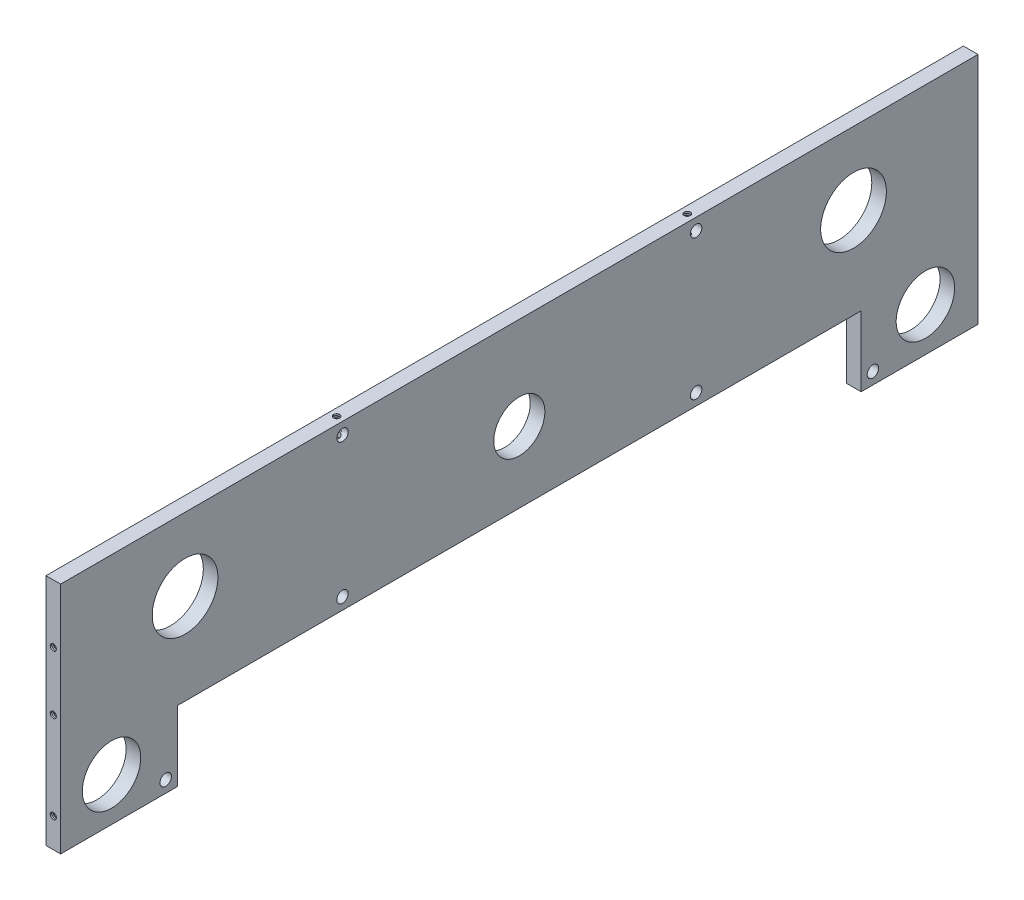
SolidWorks part; units mm, degrees
material "6061-T6 (SS)"
ref_plane "Front Plane" through (0, 0, 0) normal (0, 0, 1) x (1, 0, 0)
ref_plane "Top Plane" through (0, 0, 0) normal (0, 1, 0) x (1, 0, 0)
ref_plane "Right Plane" through (0, 0, 0) normal (1, 0, 0) x (0, 0, -1)
sketch "Sketch1" plane through (0, 0, 0) normal (1, 0, 0) x (0, 0, -1)
  line L1 (-199.39, 50.8) -> (199.39, 50.8)
  line L2 (-199.39, 50.8) -> (-199.39, -50.8)
  line L3 (-199.39, -50.8) -> (199.39, -50.8)
  line L4 (199.39, 50.8) -> (199.39, -50.8)
  line L5 (-199.39, 50.8) -> (199.39, -50.8) construction
  line L6 (-199.39, -50.8) -> (199.39, 50.8) construction
  point P0 (0, 0)
  dimension "D1" = 101.6
  dimension "D2" = 398.78
extrude "Boss-Extrude1" add sketch "Sketch1" along normal blind 6.35
sketch "Sketch2" plane through (6.35, 0, 0) normal (1, 0, 0) x (0, 0, -1)
  line L0 (-199.39, -50.8) -> (199.39, -50.8) construction
  line L1 (-145.2858, 19.1748) -> (0, 10.4973) construction
  line L2 (199.39, 50.8) -> (-199.39, 50.8) construction
  line L3 (0, 10.4973) -> (145.2858, 19.1748) construction
  line L4 (2.4449, 27.4682) -> (-141.1117, 48.1494) construction
  line L5 (0.4075, -6.6439) -> (-144.5902, -10.0906) construction
  line L10 (1.5901, 21.5351) -> (-141.9664, 42.2162) construction
  line L11 (-199.39, 50.8) -> (-199.39, -50.8) construction
  line L12 (-148.59, -50.8) -> (0, -50.8)
  line L13 (-148.59, -50.8) -> (-148.59, -20.32)
  line L14 (-148.59, -20.32) -> (148.59, -20.32)
  line L15 (0, -50.8) -> (0, -20.32) construction
  line L16 (199.39, -50.8) -> (199.39, 50.8) construction
  line L17 (-162.4251, -40.5407) -> (-132.2012, 11.5885) construction
  line L18 (0.265, -0.6512) -> (-144.7326, -4.0979) construction
  line L19 (-177.2583, -31.9405) -> (-199.39, -31.9405) construction
  line L20 (-177.2583, -31.9405) -> (-158.1418, -43.0925) construction
  line L21 (148.59, -50.8) -> (148.59, -20.32)
  line L22 (0, -50.8) -> (148.59, -50.8)
  line L23 (-77.0202, -8.4844) -> (-76.9825, -10.0714) construction
  line L24 (-77.5914, 40.6024) -> (-77.8178, 39.0311) construction
  circle A1 centre (-145.2858, 19.1748) radius 14.2875
  circle A2 centre (145.2858, 19.1748) radius 14.2875
  circle A3 centre (-145.2858, 19.1748) radius 29.2737 construction
  circle A4 centre (0, 10.4973) radius 30.48 construction
  circle A5 centre (145.2858, 19.1748) radius 29.2737 construction
  circle A11 centre (-177.2583, -31.9405) radius 12.7
  circle A12 centre (176.53, -31.9405) radius 12.7
  circle A13 centre (0, 10.4973) radius 11.1125
  circle A14 centre (-177.2583, -31.9405) radius 20.6375 construction
  circle A15 centre (-177.2583, -31.9405) radius 17.1461 construction
  circle A16 centre (-145.2858, 19.1748) radius 15.1248 construction
  circle A17 centre (0, 10.4973) radius 17.1461 construction
  circle A18 centre (34.3662, 10.4973) radius 8.7754 construction
  circle A19 centre (-153.715, -45.675) radius 5.125 construction
  circle A20 centre (-153.715, -45.675) radius 2.4892
  circle A21 centre (-76.8607, 45.675) radius 5.125 construction
  circle A22 centre (-76.8607, -15.195) radius 5.125 construction
  circle A23 centre (-76.8607, -15.195) radius 2.4892
  circle A24 centre (-76.8607, 45.675) radius 2.4892
  circle A25 centre (76.8607, 45.675) radius 2.4892
  circle A26 centre (76.8607, -15.195) radius 2.4892
  circle A27 centre (153.715, -45.675) radius 2.4892
  circle A28 centre (34.3662, 10.4973) radius 22.15 construction
  point P11 (0, 0)
  point P12 (0, -19.9827)
  point P14 (0, 40.9773)
  point P52 (-197.8958, -31.9405)
  point P56 (-159.5733, 19.1748)
  dimension "D1" = 28.575
  dimension "D5" = 58.5474
  dimension "D7" = 9.8227
  dimension "D14" = 25.4
  dimension "D15" = 60.2911
  dimension "D17" = 25.4
  dimension "D20" = 22.225
  dimension "D21" = 28.575
  dimension "D22" = 60.96
  dimension "D23" = 41.275
  dimension "D27" = 34.2921
  dimension "D28" = 30.2496
  dimension "D12" = 17.5508
  dimension "D13" = 10.25
  dimension "D29" = 4.9784
  dimension "D26" = 1.5875
  dimension "D30" = 4.9784
  dimension "D31" = 44.3
  dimension "D3" = 39.8167
  dimension "D4" = 145.5447
  dimension "D6" = 0
  dimension "D8" = 0.3373
  dimension "D9" = 5.9944
  dimension "D10" = 5.9944
  dimension "D11" = 34.3662
  dimension "D16" = 1.4942
  dimension "D18" = 18.8595
  dimension "D19" = 22.86
  dimension "D24" = 30.48
  dimension "D25" = 50.8
extrude "Cut-Extrude1" cut sketch "Sketch2" against normal through all
sketch "Sketch3" plane through (6.35, 0, 0) normal (1, 0, 0) x (0, 0, -1)
  line L0 (-193.294, 19.05) -> (-193.294, -19.05) construction
  line L1 (-199.39, 50.8) -> (-199.39, -50.8) construction
  point P2 (-193.294, 0)
  point P3 (-199.39, 0)
  dimension "D1" = 38.1
  dimension "D2" = 6.096
sketch "Sketch24" plane through (0, 50.8, 0) normal (0, 1, 0) x (1, 0, 0)
  line L0 (6.35, 199.39) -> (0, 199.39) construction
  line L1 (6.35, -199.39) -> (0, -199.39) construction
  line L2 (6.35, 199.39) -> (6.35, -199.39) construction
  point P0 (3.175, 76.2)
  point P1 (3.175, -76.2)
  dimension "D1" = 123.19
  dimension "D2" = 123.19
  dimension "D3" = 3.175
hole_wizard "#36 (0.1065) Diameter Hole1" positions "Sketch25" profile "Sketch26" hole size "#36" standard "ANSI Inch"
sketch "Sketch25" plane through (0, 50.8, 0) normal (0, 1, 0) x (1, 0, 0)
  point P0 (3.175, 76.2)
  point P3 (3.175, -76.2)
sketch "Sketch26" plane through (3.175, 50.8, -76.2) normal (1, 0, 0) x (0, 0, 1)
  line L0 (0, 0) -> (0, 9.7027)
  line L1 (0, 9.7027) -> (1.3525, 8.89)
  line L2 (1.3525, 8.89) -> (1.3525, 0)
  line L5 (1.3525, 0) -> (0, 0)
  line L10 (0, 9.7027) -> (-1.3526, 8.89) construction
  line L11 (0, -6.35) -> (0, 107.95) construction
  dimension "Hole Dia." = 2.7051
  dimension "Hole Depth" = 8.89
  dimension "Drill Angle" = 118
thread "Thread1" pitch 0.7937 method cut profile "Thread Profile1" start angle 0, offset 0, length 6.35, pitch 0.7937, diameter 2.7051
ref_plane "Plane1" through (1.8225, 50.8, -76.2) normal (0, 0, 1) x (-1, 0, 0)
sketch "Thread Profile1" plane through (1.8225, 50.8, -76.2) normal (0, 0, 1) x (-1, 0, 0)
  line L0 (0, 0) -> (0, 0.7937) construction
  line L1 (0, 0) -> (0.4296, 0.248)
  line L2 (0.4296, 0.248) -> (0.4296, 0.3473)
  line L3 (0.4296, 0.3473) -> (0, 0.5953)
  line L4 (0.4296, 0.2977) -> (0, 0.2977) construction
  line L11 (0, 0) -> (0, 0.5953)
  point P2 (0, 0)
  dimension "Pitch" = 0.7937
  dimension "Profile_Angle" = 60
  dimension "Profile_Land" = 0.0992
  dimension "Profile_Height" = 0.4296
thread "Thread2" pitch 0.7937 method cut profile "Thread Profile2" start angle 0, offset 0, length 6.35, pitch 0.7937, diameter 2.7051
ref_plane "Plane2" through (1.8225, 50.8, 76.2) normal (0, 0, 1) x (-1, 0, 0)
sketch "Thread Profile2" plane through (1.8225, 50.8, 76.2) normal (0, 0, 1) x (-1, 0, 0)
  line L0 (0, 0) -> (0, 0.7937) construction
  line L1 (0, 0) -> (0.4296, 0.248)
  line L2 (0.4296, 0.248) -> (0.4296, 0.3473)
  line L3 (0.4296, 0.3473) -> (0, 0.5953)
  line L4 (0.4296, 0.2977) -> (0, 0.2977) construction
  line L11 (0, 0) -> (0, 0.5953)
  point P2 (0, 0)
  dimension "Pitch" = 0.7937
  dimension "Profile_Angle" = 60
  dimension "Profile_Land" = 0.0992
  dimension "Profile_Height" = 0.4296
sketch "Sketch27" plane through (0, 0, -199.39) normal (0, 0, -1) x (-1, 0, 0)
  line L0 (-6.35, 50.8) -> (0, 50.8) construction
  line L1 (-6.35, -50.8) -> (-6.35, 50.8) construction
  point P0 (-3.175, 25.4)
  point P1 (-3.175, 0)
  point P2 (-3.175, -38.1)
  dimension "D1" = 25.4
  dimension "D2" = 3.175
hole_wizard "#36 (0.1065) Diameter Hole2" positions "Sketch28" profile "Sketch29" hole size "#36" standard "ANSI Inch"
sketch "Sketch28" plane through (0, 0, -199.39) normal (0, 0, -1) x (-1, 0, 0)
  point P0 (-3.175, 25.4)
  point P3 (-3.175, 0)
  point P6 (-3.175, -38.1)
sketch "Sketch29" plane through (3.175, 25.4, -199.39) normal (1, 0, 0) x (0, 1, 0)
  line L0 (0, 0) -> (0, 9.7027)
  line L1 (0, 9.7027) -> (1.3525, 8.89)
  line L2 (1.3525, 8.89) -> (1.3525, 0)
  line L5 (1.3525, 0) -> (0, 0)
  line L10 (0, 9.7027) -> (-1.3526, 8.89) construction
  line L11 (0, -6.35) -> (0, 107.95) construction
  dimension "Hole Dia." = 2.7051
  dimension "Hole Depth" = 8.89
  dimension "Drill Angle" = 118
thread "Thread3" pitch 0.7937 method cut profile "Thread Profile3" start angle 0, offset 0, length 6.35, pitch 0.7937, diameter 2.7051
ref_plane "Plane3" through (4.5275, 25.4, -199.39) normal (0, -1, 0) x (1, 0, 0)
sketch "Thread Profile3" plane through (4.5275, 25.4, -199.39) normal (0, -1, 0) x (1, 0, 0)
  line L0 (0, 0) -> (0, 0.7937) construction
  line L1 (0, 0) -> (0.4296, 0.248)
  line L2 (0.4296, 0.248) -> (0.4296, 0.3473)
  line L3 (0.4296, 0.3473) -> (0, 0.5953)
  line L4 (0.4296, 0.2977) -> (0, 0.2977) construction
  line L11 (0, 0) -> (0, 0.5953)
  point P2 (0, 0)
  dimension "Pitch" = 0.7937
  dimension "Profile_Angle" = 60
  dimension "Profile_Land" = 0.0992
  dimension "Profile_Height" = 0.4296
thread "Thread4" pitch 0.7937 method cut profile "Thread Profile4" start angle 0, offset 0, length 6.35, pitch 0.7937, diameter 2.7051
ref_plane "Plane4" through (4.5275, 0, -199.39) normal (0, -1, 0) x (1, 0, 0)
sketch "Thread Profile4" plane through (4.5275, 0, -199.39) normal (0, -1, 0) x (1, 0, 0)
  line L0 (0, 0) -> (0, 0.7937) construction
  line L1 (0, 0) -> (0.4296, 0.248)
  line L2 (0.4296, 0.248) -> (0.4296, 0.3473)
  line L3 (0.4296, 0.3473) -> (0, 0.5953)
  line L4 (0.4296, 0.2977) -> (0, 0.2977) construction
  line L11 (0, 0) -> (0, 0.5953)
  point P2 (0, 0)
  dimension "Pitch" = 0.7937
  dimension "Profile_Angle" = 60
  dimension "Profile_Land" = 0.0992
  dimension "Profile_Height" = 0.4296
thread "Thread5" pitch 0.7937 method cut profile "Thread Profile5" start angle 0, offset 0, length 6.35, pitch 0.7937, diameter 2.7051
ref_plane "Plane5" through (4.5275, -38.1, -199.39) normal (0, -1, 0) x (1, 0, 0)
sketch "Thread Profile5" plane through (4.5275, -38.1, -199.39) normal (0, -1, 0) x (1, 0, 0)
  line L0 (0, 0) -> (0, 0.7937) construction
  line L1 (0, 0) -> (0.4296, 0.248)
  line L2 (0.4296, 0.248) -> (0.4296, 0.3473)
  line L3 (0.4296, 0.3473) -> (0, 0.5953)
  line L4 (0.4296, 0.2977) -> (0, 0.2977) construction
  line L11 (0, 0) -> (0, 0.5953)
  point P2 (0, 0)
  dimension "Pitch" = 0.7937
  dimension "Profile_Angle" = 60
  dimension "Profile_Land" = 0.0992
  dimension "Profile_Height" = 0.4296
sketch "Sketch36" plane through (0, 0, 199.39) normal (0, 0, 1) x (1, 0, 0)
  line L0 (6.35, 50.8) -> (6.35, -50.8) construction
  line L1 (6.35, 50.8) -> (0, 50.8) construction
  point P0 (3.175, 25.4)
  point P1 (3.175, -12.7)
  point P2 (3.175, -50.8)
  dimension "D1" = 25.4
  dimension "D2" = 3.175
  dimension "D3" = 38.1
  dimension "D4" = 38.1
hole_wizard "#36 (0.1065) Diameter Hole3" positions "Sketch37" profile "Sketch38" hole size "#36" standard "ANSI Inch"
sketch "Sketch37" plane through (0, 0, 199.39) normal (0, 0, 1) x (1, 0, 0)
  point P0 (3.175, 25.4)
  point P3 (3.175, 0)
  point P6 (3.175, -38.1)
sketch "Sketch38" plane through (3.175, 25.4, 199.39) normal (1, 0, 0) x (0, -1, 0)
  line L0 (0, 0) -> (0, 9.7027)
  line L1 (0, 9.7027) -> (1.3525, 8.89)
  line L2 (1.3525, 8.89) -> (1.3525, 0)
  line L5 (1.3525, 0) -> (0, 0)
  line L10 (0, 9.7027) -> (-1.3525, 8.89) construction
  line L11 (0, -6.35) -> (0, 107.95) construction
  dimension "Hole Dia." = 2.7051
  dimension "Hole Depth" = 8.89
  dimension "Drill Angle" = 118
thread "Thread6" pitch 0.7937 method cut profile "Thread Profile6" start angle 0, offset 0, length 6.35, pitch 0.7937, diameter 2.7051
ref_plane "Plane6" through (1.8225, 25.4, 199.39) normal (0, -1, 0) x (-1, 0, 0)
sketch "Thread Profile6" plane through (1.8225, 25.4, 199.39) normal (0, -1, 0) x (-1, 0, 0)
  line L0 (0, 0) -> (0, 0.7937) construction
  line L1 (0, 0) -> (0.4296, 0.248)
  line L2 (0.4296, 0.248) -> (0.4296, 0.3473)
  line L3 (0.4296, 0.3473) -> (0, 0.5953)
  line L4 (0.4296, 0.2977) -> (0, 0.2977) construction
  line L11 (0, 0) -> (0, 0.5953)
  point P2 (0, 0)
  dimension "Pitch" = 0.7937
  dimension "Profile_Angle" = 60
  dimension "Profile_Land" = 0.0992
  dimension "Profile_Height" = 0.4296
thread "Thread7" pitch 0.7937 method cut profile "Thread Profile7" start angle 0, offset 0, length 6.35, pitch 0.7937, diameter 2.7051
ref_plane "Plane7" through (1.8225, 0, 199.39) normal (0, -1, 0) x (-1, 0, 0)
sketch "Thread Profile7" plane through (1.8225, 0, 199.39) normal (0, -1, 0) x (-1, 0, 0)
  line L0 (0, 0) -> (0, 0.7937) construction
  line L1 (0, 0) -> (0.4296, 0.248)
  line L2 (0.4296, 0.248) -> (0.4296, 0.3473)
  line L3 (0.4296, 0.3473) -> (0, 0.5953)
  line L4 (0.4296, 0.2977) -> (0, 0.2977) construction
  line L11 (0, 0) -> (0, 0.5953)
  point P2 (0, 0)
  dimension "Pitch" = 0.7937
  dimension "Profile_Angle" = 60
  dimension "Profile_Land" = 0.0992
  dimension "Profile_Height" = 0.4296
thread "Thread8" pitch 0.7937 method cut profile "Thread Profile8" start angle 0, offset 0, length 6.35, pitch 0.7937, diameter 2.7051
ref_plane "Plane8" through (1.8225, -38.1, 199.39) normal (0, -1, 0) x (-1, 0, 0)
sketch "Thread Profile8" plane through (1.8225, -38.1, 199.39) normal (0, -1, 0) x (-1, 0, 0)
  line L0 (0, 0) -> (0, 0.7937) construction
  line L1 (0, 0) -> (0.4296, 0.248)
  line L2 (0.4296, 0.248) -> (0.4296, 0.3473)
  line L3 (0.4296, 0.3473) -> (0, 0.5953)
  line L4 (0.4296, 0.2977) -> (0, 0.2977) construction
  line L11 (0, 0) -> (0, 0.5953)
  point P2 (0, 0)
  dimension "Pitch" = 0.7937
  dimension "Profile_Angle" = 60
  dimension "Profile_Land" = 0.0992
  dimension "Profile_Height" = 0.4296
